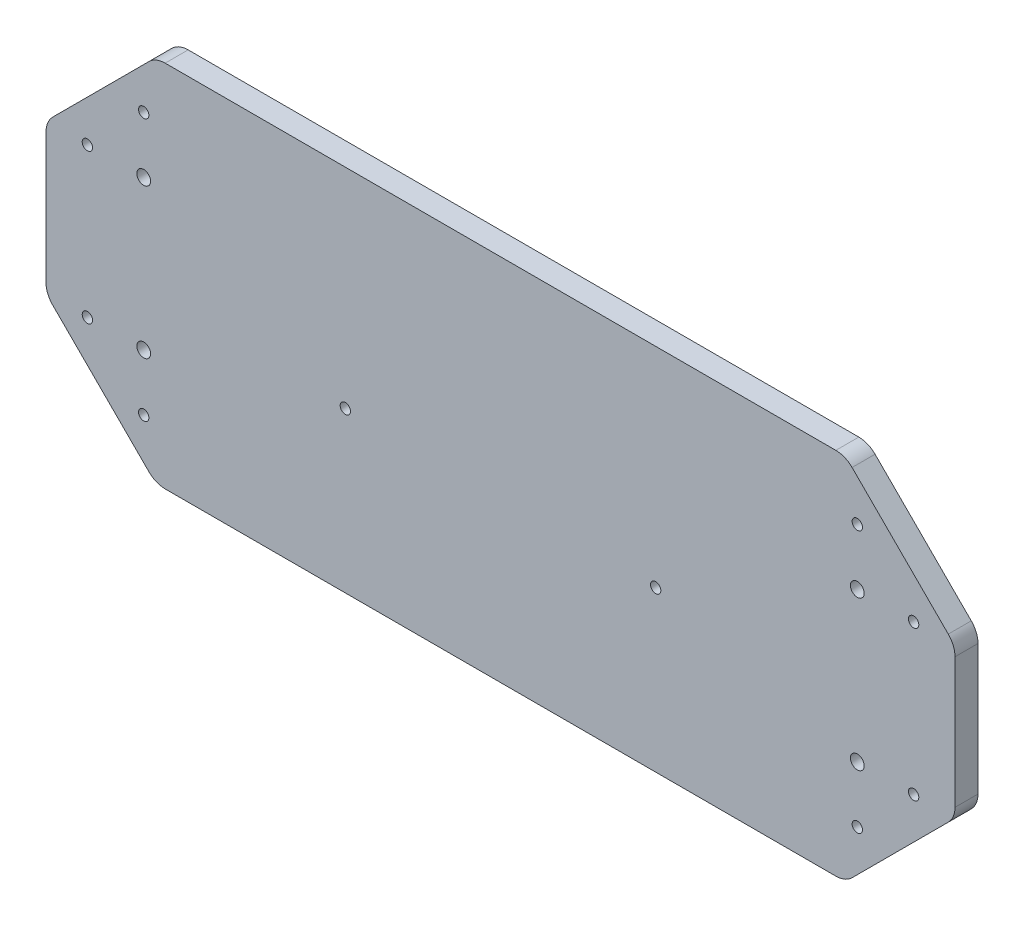
SolidWorks part; units mm, degrees
ref_plane "Plan de face" through (0, 0, 0) normal (0, 0, 1) x (1, 0, 0)
ref_plane "Plan de dessus" through (0, 0, 0) normal (0, 1, 0) x (1, 0, 0)
ref_plane "Plan de droite" through (0, 0, 0) normal (1, 0, 0) x (0, 0, -1)
sketch "Esquisse1" plane through (0, 0, 0) normal (0, 0, 1) x (1, 0, 0)
  line L0 (-197.7, 32.5) -> (-150, 80.2)
  line L1 (-197.7, 32.5) -> (197.7, 32.5)
  line L2 (-197.7, 32.5) -> (-197.7, -32.5)
  line L3 (-197.7, -32.5) -> (197.7, -32.5)
  line L4 (197.7, 32.5) -> (197.7, -32.5)
  line L5 (-150, 80.2) -> (150, 80.2)
  line L6 (-150, 80.2) -> (-150, 32.5)
  line L7 (-150, 32.5) -> (150, 32.5)
  line L8 (150, 80.2) -> (150, 32.5)
  line L9 (-150, -32.5) -> (150, -32.5)
  line L10 (-150, -32.5) -> (-150, -80.2)
  line L11 (-150, -80.2) -> (150, -80.2)
  line L12 (150, -32.5) -> (150, -80.2)
  line L13 (150, 80.2) -> (197.7, 32.5)
  line L14 (197.7, -32.5) -> (150, -80.2)
  line L15 (-150, -80.2) -> (-197.7, -32.5)
  dimension "D1" = 65
  dimension "D2" = 395.4
  dimension "D3" = 300
  dimension "D4" = 300
  dimension "D5" = 47.7
  dimension "D6" = 47.7
  dimension "D7" = 47.7
  dimension "D8" = 47.7
  dimension "D9" = 150
  dimension "D10" = 32.5
extrude "Boss.-Extru.1" add sketch "Esquisse1" along normal blind 10 contours L4 L1 L2 L3 | L8 L5 L6 L1 | L6 L0 L1 | L12 L3 L10 L11 | L15 L10 L3 | L13 L8 L1 | L14 L3 L12 region at (-165.9, 48.4, 0) region at (0, 0, 0) region at (0, 56.35, 0) region at (-165.9, -48.4, 0) region at (165.9, 48.4, 0) region at (0, -56.35, 0) region at (165.9, -48.4, 0)
sketch "Esquisse2" plane through (0, 0, 10) normal (0, 0, 1) x (1, 0, 0)
  line L1 (-165.2, 22.5) -> (-145.2, 22.5)
  line L2 (-165.2, 22.5) -> (-165.2, 42.5)
  line L3 (-165.2, 42.5) -> (-145.2, 42.5)
  line L4 (-145.2, 22.5) -> (-145.2, 42.5)
  line L5 (145.2, 22.5) -> (165.2, 22.5)
  line L6 (145.2, 22.5) -> (145.2, 42.5)
  line L7 (145.2, 42.5) -> (165.2, 42.5)
  line L8 (165.2, 22.5) -> (165.2, 42.5)
  line L9 (145.2, -22.5) -> (165.2, -22.5)
  line L10 (145.2, -22.5) -> (145.2, -42.5)
  line L11 (145.2, -42.5) -> (165.2, -42.5)
  line L12 (165.2, -22.5) -> (165.2, -42.5)
  line L13 (-165.2, -22.5) -> (-145.2, -22.5)
  line L14 (-165.2, -22.5) -> (-165.2, -42.5)
  line L15 (-165.2, -42.5) -> (-145.2, -42.5)
  line L16 (-145.2, -22.5) -> (-145.2, -42.5)
  dimension "D1" = 20
  dimension "D2" = 20
  dimension "D3" = 20
  dimension "D4" = 20
  dimension "D5" = 20
  dimension "D6" = 20
  dimension "D7" = 20
  dimension "D8" = 20
  dimension "D9" = 10
  dimension "D10" = 10
  dimension "D11" = 10
  dimension "D12" = 10
  dimension "D13" = 15.2
  dimension "D14" = 15.2
  dimension "D15" = 15.2
  dimension "D16" = 15.2
sketch "Esquisse3" plane through (0, 0, 10) normal (0, 0, 1) x (1, 0, 0)
  line L0 (-165.2, 42.5) -> (-145.2, 42.5) construction
  line L2 (-145.2, 22.5) -> (-145.2, 42.5) construction
  line L3 (-165.2, 22.5) -> (-165.2, 42.5) construction
  line L4 (-165.2, -22.5) -> (-145.2, -22.5) construction
  line L5 (-145.2, -22.5) -> (-145.2, -42.5) construction
  line L6 (-165.2, -22.5) -> (-165.2, -42.5) construction
  line L7 (-165.2, -42.5) -> (-145.2, -42.5) construction
  line L8 (145.2, -22.5) -> (165.2, -22.5) construction
  line L9 (145.2, -22.5) -> (145.2, -42.5) construction
  line L10 (165.2, -22.5) -> (165.2, -42.5) construction
  line L11 (145.2, -42.5) -> (165.2, -42.5) construction
  line L12 (145.2, 22.5) -> (145.2, 42.5) construction
  line L13 (145.2, 42.5) -> (165.2, 42.5) construction
  line L14 (165.2, 22.5) -> (165.2, 42.5) construction
  circle A0 centre (-179.7, 32.5) radius 2.25
  circle A1 centre (-155.2, 32.5) radius 3
  circle A2 centre (-155.2, 57) radius 2.25
  circle A3 centre (-155.2, -32.5) radius 3
  circle A4 centre (-179.7, -32.5) radius 2.25
  circle A5 centre (-155.2, -57) radius 2.25
  circle A6 centre (155.2, -32.5) radius 3
  circle A7 centre (179.7, -32.5) radius 2.25
  circle A8 centre (155.2, -57) radius 2.25
  circle A9 centre (155.2, 32.5) radius 3
  circle A10 centre (179.7, 32.5) radius 2.25
  circle A11 centre (155.2, 57) radius 2.25
  dimension "D1" = 6
  dimension "D5" = 4.5
  dimension "D6" = 4.5
  dimension "D10" = 6
  dimension "D13" = 4.5
  dimension "D14" = 4.5
  dimension "D17" = 14.5
  dimension "D19" = 6
  dimension "D22" = 4.5
  dimension "D27" = 4.5
  dimension "D28" = 4.5
  dimension "D29" = 4.5
  dimension "D30" = 6
  dimension "D2" = 10
  dimension "D3" = 10
  dimension "D4" = 10
  dimension "D7" = 14.5
  dimension "D8" = 14.5
  dimension "D9" = 10
  dimension "D11" = 10
  dimension "D12" = 10
  dimension "D15" = 10
  dimension "D16" = 10
  dimension "D18" = 14.5
  dimension "D20" = 10
  dimension "D21" = 10
  dimension "D23" = 10
  dimension "D24" = 14.5
  dimension "D25" = 14.5
  dimension "D26" = 10
  dimension "D31" = 10
  dimension "D32" = 10
  dimension "D33" = 10
  dimension "D34" = 14.5
  dimension "D35" = 10
  dimension "D36" = 14.5
extrude "Enlèv. mat.-Extru.1" cut sketch "Esquisse3" against normal blind 10
sketch "Esquisse4" plane through (0, 0, 10) normal (0, 0, 1) x (1, 0, 0)
  line L0 (-197.7, 32.5) -> (-197.7, -32.5) construction
  line L1 (-150, -80.2) -> (150, -80.2) construction
  line L2 (197.7, 32.5) -> (197.7, -32.5) construction
  circle A0 centre (-67.5, -10.7) radius 2.25
  circle A1 centre (67.5, -10.7) radius 2.25
  dimension "D1" = 4.5
  dimension "D2" = 4.5
  dimension "D3" = 130.2
  dimension "D4" = 69.5
  dimension "D5" = 69.5
  dimension "D6" = 130.2
extrude "Enlèv. mat.-Extru.2" cut sketch "Esquisse4" against normal blind 10
fillet "Congé1" radius 10 4 edges at (-150, 80.2, 5) (150, 80.2, 5) (150, -80.2, 5) (-150, -80.2, 5)
fillet "Congé2" radius 10 4 edges at (-197.7, -32.5, 5) (-197.7, 32.5, 5) (197.7, -32.5, 5) (197.7, 32.5, 5)
